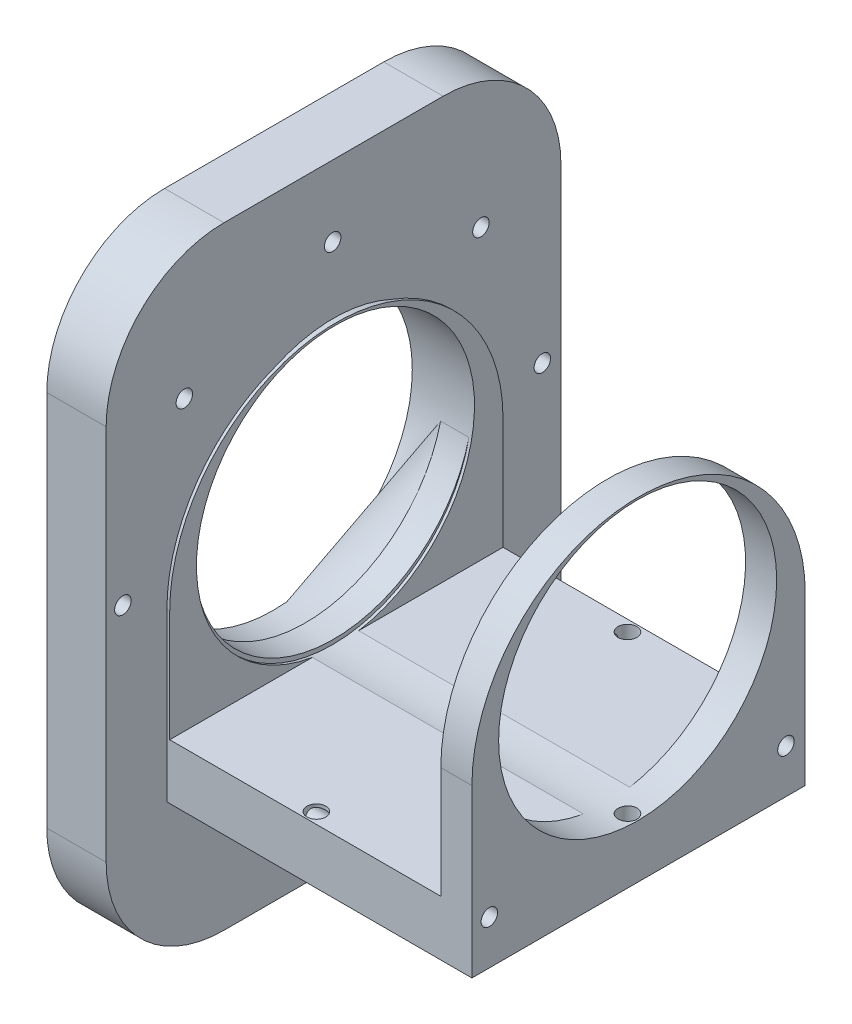
SolidWorks part; units mm, degrees
ref_plane "前视基准面" through (0, 0, 0) normal (0, 0, 1) x (1, 0, 0)
ref_plane "上视基准面" through (0, 0, 0) normal (0, 1, 0) x (1, 0, 0)
ref_plane "右视基准面" through (0, 0, 0) normal (1, 0, 0) x (0, 0, -1)
sketch "草图1" plane through (0, 0, 0) normal (0, 0, 1) x (1, 0, 0)
  line L1 (-35.36, 35.36) -> (35.36, 35.36)
  line L2 (-35.36, 35.36) -> (-35.36, -35.36)
  line L3 (-35.36, -35.36) -> (35.36, -35.36)
  line L4 (35.36, 35.36) -> (35.36, -35.36)
  line L5 (-35.36, 35.36) -> (35.36, -35.36) construction
  line L6 (-35.36, -35.36) -> (35.36, 35.36) construction
  point P0 (0, 0)
  dimension "D1" = 70.72
  dimension "D2" = 70.72
extrude "凸台-拉伸1" add sketch "草图1" along normal blind 70.72
sketch "草图2" plane through (0, 0, 0) normal (0, 0, 1) x (1, 0, 0)
  line L0 (35.36, 35.36) -> (28.76, 35.36) construction
  line L1 (35.36, 35.36) -> (-35.36, 35.36) construction
  line L3 (-35.36, -35.36) -> (35.36, -35.36) construction
  line L4 (0, -35.36) -> (0, 0) construction
  line L5 (28.76, 35.36) -> (28.76, -23.64)
  line L7 (-35.36, 35.36) -> (-28.76, 35.36) construction
  line L8 (-28.76, 35.36) -> (-28.76, -23.64)
  line L9 (-28.76, -23.64) -> (28.76, -23.64)
  line L10 (-28.76, 35.36) -> (28.76, 35.36)
  dimension "D1" = 6.6
  dimension "D2" = 59
extrude "切除-拉伸2" cut sketch "草图2" along normal blind 125.72 and the other way blind 26
fillet "圆角1" 2 edges at (-32.06, 35.36, 70.72) (-32.06, 35.36, 0) type full round first side face at (0, 2.93, 70.72) second side face at (0, 2.93, 0) middle face at (-32.06, 35.36, 35.36)
fillet "圆角2" 2 edges at (32.06, 35.36, 70.72) (32.06, 35.36, 0) type full round first side face at (0, -5.91, 70.72) second side face at (0, -5.91, 0) middle face at (32.06, 35.36, 35.36)
sketch "草图3" plane through (35.36, 0, 0) normal (1, 0, 0) x (0, 0, -1)
  line L0 (0, 0) -> (-71.1101, 0) construction
  line L1 (-35.5551, 0) -> (-35.5551, 35.3595) construction
  arc A0 (0, 0) -> (-70.72, 0) centre (-35.36, 0) ccw construction
  circle A1 centre (-35.5551, 5.4485) radius 29.5
  dimension "D2" = 59
  dimension "D1" = 71.1101
sketch "草图6" plane through (0, 0, 70.72) normal (0, 0, 1) x (1, 0, 0)
  line L0 (28.76, -23.64) -> (35.36, -23.64) construction
  line L1 (35.36, -24.0515) -> (35.36, 34.9485) construction
sketch "草图7" plane through (0, 0, 0) normal (0, 0, -1) x (-1, 0, 0)
  line L0 (-28.76, -23.64) -> (-35.5987, -23.64) construction
extrude "切除-拉伸4" cut sketch "草图3" along normal blind 1 and the other way blind 267 contours A1
sketch "草图8" plane through (0, -35.36, 0) normal (0, -1, 0) x (1, 0, 0)
  line L0 (0, 0) -> (0, 70.72) construction
  line L1 (-35.36, 70.72) -> (35.36, 70.72) construction
  circle A0 centre (0, 35.36) radius 3
extrude "凸台-拉伸2" add sketch "草图8" along normal blind 6
sketch "草图9" plane through (0, 0, 0) normal (0, 0, -1) x (-1, 0, 0)
  line L0 (4.2232, -23.64) -> (4.0853, -23.64)
  line L1 (28.76, -23.64) -> (-28.76, -23.64) construction
sketch "草图11" plane through (35.36, 0, 0) normal (1, 0, 0) x (0, 0, -1)
  line L0 (-35.5551, 34.9485) -> (-35.5551, -24.0515) construction
  circle A0 centre (-35.5551, 5.4485) radius 29.5 construction
  circle A1 centre (-35.5551, 5.4485) radius 44.5 construction
  circle A2 centre (-35.5551, -39.0515) radius 1.75
  circle A3 centre (-67.0213, -26.0178) radius 1.75
  circle A4 centre (-80.0551, 5.4485) radius 1.75
  circle A5 centre (-67.0213, 36.9147) radius 1.75
  circle A6 centre (-35.5551, 49.9485) radius 1.75
  circle A7 centre (-4.0888, 36.9147) radius 1.75
  circle A8 centre (8.9449, 5.4485) radius 1.75
  circle A9 centre (-4.0888, -26.0178) radius 1.75
  point P26 (-35.5551, 5.4485)
  dimension "D1" = 3.5
  dimension "D2" = 8
extrude "切除-拉伸5" cut sketch "草图11" against normal blind 88
ref_plane "基准面2" through (-35.36, 0, 0) normal (-1, 0, 0) x (0, 0, 1)
sketch "草图14" plane through (-35.36, 0, 0) normal (-1, 0, 0) x (0, 0, 1)
  line L0 (35.36, -35.36) -> (35.36, 35.36) construction
  line L1 (70.72, -35.36) -> (0, -35.36) construction
  line L2 (0, 0) -> (70.72, 0) construction
  line L4 (-12.89, 65.01) -> (83.61, 65.01)
  line L5 (-12.89, 65.01) -> (-12.89, -65.01)
  line L6 (-12.89, -65.01) -> (83.61, -65.01)
  line L7 (83.61, 65.01) -> (83.61, -65.01)
  line L8 (-12.89, 65.01) -> (83.61, -65.01) construction
  line L9 (-12.89, -65.01) -> (83.61, 65.01) construction
  arc A0 (70.72, 0) -> (0, 0) centre (35.36, 0) ccw construction
  point P11 (35.36, 0)
  dimension "D1" = 96.5
  dimension "D2" = 130.02
extrude "凸台-拉伸3" add sketch "草图14" along normal blind 6.6
sketch "草图21" plane through (-35.36, 0, 0) normal (1, 0, 0) x (0, 0, -1)
  line L0 (-35.5551, -24.0515) -> (-35.5551, 34.9485) construction
  circle A0 centre (-35.5551, 5.4485) radius 29.5 construction
  circle A1 centre (-35.5551, 5.4485) radius 29.5
  dimension "D1" = 59
extrude "切除-拉伸7" cut sketch "草图21" against normal blind 51
sketch "草图24" plane through (-41.96, 0, 0) normal (-1, 0, 0) x (0, 0, 1)
  line L0 (35.5551, -24.0515) -> (35.5551, 34.9485) construction
  line L1 (6.0551, 5.4485) -> (65.0551, 5.4485) construction
  circle A0 centre (35.5551, 5.4485) radius 29.5 construction
  circle A1 centre (35.5551, 5.4485) radius 44.5 construction
  circle A2 centre (35.5551, 49.9485) radius 1.75
  circle A3 centre (67.0213, 36.9147) radius 1.75
  circle A4 centre (80.0551, 5.4485) radius 1.75
  circle A5 centre (67.0213, -26.0178) radius 1.75
  circle A6 centre (35.5551, -39.0515) radius 1.75
  circle A7 centre (4.0888, -26.0178) radius 1.75
  circle A8 centre (-8.9449, 5.4485) radius 1.75
  circle A9 centre (4.0888, 36.9147) radius 1.75
  point P27 (35.5551, 5.4485)
  dimension "D1" = 3.5
  dimension "D2" = 8
extrude "切除-拉伸8" cut sketch "草图24" against normal blind 10
ref_plane "基准面3" through (-35.36, 0, 0) normal (1, 0, 0) x (0, 0, -1)
sketch "草图26" plane through (-35.36, 0, 0) normal (1, 0, 0) x (0, 0, -1)
  line L0 (-83.61, 65.01) -> (12.89, 65.01) construction
  line L1 (12.89, 65.01) -> (12.89, -65.01) construction
  line L2 (-35.36, 65.01) -> (-35.36, -65.01) construction
  line L3 (12.89, -65.01) -> (-83.61, -65.01) construction
  line L4 (12.89, 0) -> (-89.1335, 0) construction
  line L6 (-83.61, 65.01) -> (12.89, 65.01)
  line L7 (-83.61, 65.01) -> (-83.61, -65.01)
  line L8 (-83.61, -65.01) -> (12.89, -65.01)
  line L9 (12.89, 65.01) -> (12.89, -65.01)
  line L10 (-83.61, 65.01) -> (12.89, -65.01) construction
  line L11 (-83.61, -65.01) -> (12.89, 65.01) construction
  circle A0 centre (-35.36, 6.3378) radius 29.5
  point P10 (-35.36, 0)
  dimension "D1" = 59
extrude "凸台-拉伸4" add sketch "草图26" along normal blind 6
sketch "草图27" plane through (-35.36, 0, 0) normal (1, 0, 0) x (0, 0, -1)
  line L0 (-35.5551, 5.4485) -> (-35.5551, -16.3211) construction
  circle A0 centre (-35.5551, 5.4485) radius 44.5 construction
  circle A1 centre (-35.5551, 49.9485) radius 1.75
  circle A2 centre (-4.0888, 36.9147) radius 1.75
  circle A3 centre (8.9449, 5.4485) radius 1.75
  circle A4 centre (-4.0888, -26.0178) radius 1.75
  circle A5 centre (-35.5551, -39.0515) radius 1.75
  circle A6 centre (-67.0213, -26.0178) radius 1.75
  circle A7 centre (-80.0551, 5.4485) radius 1.75
  circle A8 centre (-67.0213, 36.9147) radius 1.75
  point P23 (-35.5551, 5.4485)
  dimension "D1" = 3.5
  dimension "D2" = 8
extrude "切除-拉伸13" cut sketch "草图27" along normal blind 32
sketch "草图29" plane through (0, -35.36, 0) normal (0, -1, 0) x (-1, 0, 0)
  circle A0 centre (0, -35.36) radius 33 construction
  circle A1 centre (0, -68.36) radius 2
  circle A2 centre (-33, -35.36) radius 2
  circle A3 centre (0, -2.36) radius 2
  circle A5 centre (33, -35.36) radius 2 [skipped]
  point P14 (0, -35.36)
  dimension "D1" = 4
  dimension "D2" = 4
extrude "切除-拉伸15" cut sketch "草图29" against normal up to surface (11.72 mm away) up to face at (0, -23.64, 15.3224)
sketch "草图30" plane through (35.36, 0, 0) normal (1, 0, 0) x (0, 0, -1)
  line L0 (-70.72, -23.64) -> (0, -23.64)
fillet "圆角3" radius 25 1 edges at (-35.66, 65.01, -12.89) type face fillet first side face at (-35.66, 65.01, 35.36) second side face at (-35.66, 0, -12.89)
fillet "圆角4" radius 25 1 edges at (-35.66, 65.01, 83.61) type face fillet first side face at (-35.66, 0, 83.61) second side face at (-35.66, 65.01, 47.86)
fillet "圆角5" radius 25 1 edges at (-35.66, -65.01, -12.89) type face fillet first side face at (-35.66, -12.5, -12.89) second side face at (-35.66, -65.01, 35.36)
fillet "圆角6" radius 25 1 edges at (-35.66, -65.01, 83.61) type face fillet first side face at (-35.66, -65.01, 47.86) second side face at (-35.66, -12.5, 83.61)
